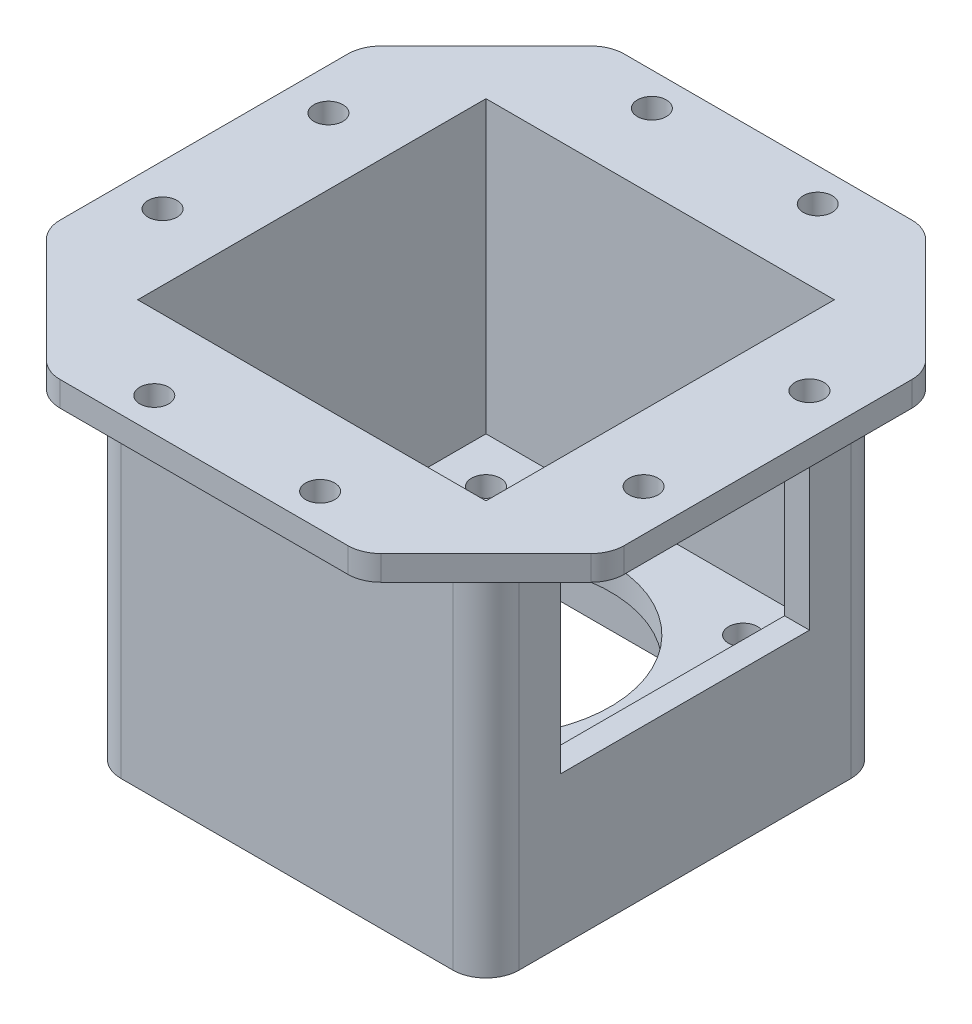
SolidWorks part; units mm, degrees
ref_plane "Front Plane" through (0, 0, 0) normal (0, 0, 1) x (1, 0, 0)
ref_plane "Top Plane" through (0, 0, 0) normal (0, 1, 0) x (1, 0, 0)
ref_plane "Right Plane" through (0, 0, 0) normal (1, 0, 0) x (0, 0, -1)
sketch "Sketch2" plane through (0, 0, 0) normal (0, 1, 0) x (1, 0, 0)
  line L0 (-24, 24) -> (24, 24)
  line L1 (-21, 21) -> (21, 21) construction
  line L2 (-21, 21) -> (-21, -21) construction
  line L3 (-21, -21) -> (21, -21) construction
  line L4 (21, 21) -> (21, -21) construction
  line L5 (-21, 21) -> (21, -21) construction
  line L6 (-21, -21) -> (21, 21) construction
  line L7 (24, 24) -> (24, -24)
  line L8 (-24, -24) -> (24, -24)
  line L9 (-24, 24) -> (-24, -24)
  line L10 (-15.5, 15.5) -> (15.5, 15.5) construction
  line L11 (-15.5, 15.5) -> (-15.5, -15.5) construction
  line L12 (-15.5, -15.5) -> (15.5, -15.5) construction
  line L13 (15.5, -15.5) -> (15.5, 15.5) construction
  circle A0 centre (0, 0) radius 15
  circle A1 centre (-15.5, 15.5) radius 1.75
  circle A2 centre (15.5, 15.5) radius 1.75
  circle A3 centre (15.5, -15.5) radius 1.75
  circle A4 centre (-15.5, -15.5) radius 1.75
  point P0 (0, 0)
  point P16 (-15.7537, -15.7537)
  point P20 (16.9392, -17.2228)
  point P23 (15.5, -15.9435)
  point P24 (16.7779, -17.2228)
  point P25 (0, 0)
  point P26 (15.7044, -15.5822)
  dimension "D3" = 30
  dimension "D4" = 3.5
  dimension "D1" = 42
  dimension "D2" = 3
  dimension "D5" = 31
extrude "Boss-Extrude1" add sketch "Sketch2" along normal blind 3
sketch "Sketch3" plane through (0, 3, 0) normal (0, 1, 0) x (1, 0, 0)
  line L1 (-21, -21) -> (21, -21)
  line L2 (-21, -21) -> (-21, 21)
  line L3 (-21, 21) -> (21, 21)
  line L4 (21, -21) -> (21, 21)
  line L5 (-21, -21) -> (21, 21) construction
  line L6 (-21, 21) -> (21, -21) construction
  line L7 (-24, -24) -> (24, -24)
  line L8 (-24, -24) -> (-24, 24)
  line L9 (-24, 24) -> (24, 24)
  line L10 (24, -24) -> (24, 24)
  line L11 (-24, -24) -> (24, 24) construction
  line L12 (-24, 24) -> (24, -24) construction
  point P0 (0, 0)
  point P5 (0, 0)
  dimension "D1" = 42
extrude "Boss-Extrude2" add sketch "Sketch3" along normal blind 32
sketch "Sketch4" plane through (0, 35, 0) normal (0, 1, 0) x (1, 0, 0)
  line L1 (-21, -21) -> (21, -21)
  line L2 (-21, -21) -> (-21, 21)
  line L3 (-21, 21) -> (21, 21)
  line L4 (21, -21) -> (21, 21)
  line L5 (-21, -21) -> (21, 21) construction
  line L6 (-21, 21) -> (21, -21) construction
  line L23 (-34, 0) -> (34, 0) construction
  line L24 (-34, 10) -> (34, 10) construction
  line L44 (-34, -10) -> (34, -10) construction
  line L45 (0, -34) -> (0, 34) construction
  line L46 (34, -34) -> (34, 34)
  line L47 (34, 34) -> (-34, 34)
  line L48 (-34, 34) -> (-34, -34)
  line L49 (-34, -34) -> (34, -34)
  line L50 (34, -34) -> (34, 34)
  line L51 (34, 34) -> (-34, 34)
  line L52 (-34, 34) -> (-34, -34)
  line L53 (-34, -34) -> (34, -34)
  line L54 (-10, 34) -> (-10, -34) construction
  line L55 (10, 34) -> (10, -34) construction
  line L56 (-34, 30) -> (34, 30) construction
  line L57 (-29, 10) -> (-29, -10) construction
  line L58 (29, 10) -> (29, -10) construction
  line L59 (-34, -30) -> (34, -30) construction
  circle A0 centre (-10, 30) radius 1.75
  circle A1 centre (10, 30) radius 1.75
  circle A2 centre (-29, 10) radius 1.75
  circle A3 centre (-29, -10) radius 1.75
  circle A4 centre (-10, -30) radius 1.75
  circle A5 centre (10, -30) radius 1.75
  circle A6 centre (29, -10) radius 1.75
  circle A7 centre (29, 10) radius 1.75
  point P0 (0, 0)
  point P48 (-10, -30)
  point P49 (-10, -30)
  dimension "D6" = 3.5
  dimension "D7" = 3.5
  dimension "D9" = 3.5
  dimension "D1" = 10
  dimension "D2" = 10
  dimension "D3" = 10
  dimension "D4" = 10
  dimension "D5" = 10
  dimension "D8" = 20
  dimension "D10" = 20
  dimension "D11" = 5
  dimension "D12" = 5
extrude "Boss-Extrude3" add sketch "Sketch4" along normal blind 3
chamfer "Chamfer1" distance 15 angle 45 4 edges at (34, 36.5, 34) (34, 36.5, -34) (-34, 36.5, -34) (-34, 36.5, 34)
sketch "Sketch5" plane through (0, 0, 0) normal (0, -1, 0) x (1, 0, 0)
  line L1 (-21, 21) -> (21, 21)
  line L2 (-21, 21) -> (-21, -21)
  line L3 (-21, -21) -> (21, -21)
  line L4 (21, 21) -> (21, -21)
  line L5 (-21, 21) -> (21, -21) construction
  line L6 (-21, -21) -> (21, 21) construction
  line L7 (-24, -24) -> (24, -24)
  line L8 (-24, -24) -> (-24, 24)
  line L9 (-24, 24) -> (24, 24)
  line L10 (24, -24) -> (24, 24)
  line L11 (-24, -24) -> (24, 24) construction
  line L12 (-24, 24) -> (24, -24) construction
  line L13 (24, -24) -> (-24, -24) construction
  point P0 (0, 0)
  point P5 (0, 0)
  point P11 (24, 24)
  point P13 (0, 0)
  dimension "D1" = 42
extrude "Boss-Extrude4" add sketch "Sketch5" along normal blind 10
fillet "Fillet1" radius 4 4 edges at (-24, 12.5, 24) (-24, 12.5, -24) (24, 12.5, 24) (24, 12.5, -24)
sketch "Sketch7" plane through (24, 0, 0) normal (1, 0, 0) x (0, 0, -1)
  line L0 (21, 0) -> (-21, 0) construction
  line L1 (-15, 28) -> (15, 28)
  line L2 (-15, 28) -> (-15, 8)
  line L3 (-15, 8) -> (15, 8)
  line L4 (15, 28) -> (15, 8)
  line L5 (-15, 28) -> (15, 8) construction
  line L6 (-15, 8) -> (15, 28) construction
  point P0 (0, 18)
  point P5 (0, 0)
  dimension "D1" = 20
  dimension "D2" = 30
  dimension "D3" = 28
extrude "Cut-Extrude2" cut sketch "Sketch7" against normal up to next
fillet "Fillet2" radius 4 8 edges at (-19, 36.5, 34) (-34, 36.5, 19) (-34, 36.5, -19) (-19, 36.5, -34) (19, 36.5, -34) (34, 36.5, -19) (19, 36.5, 34) (34, 36.5, 19)
